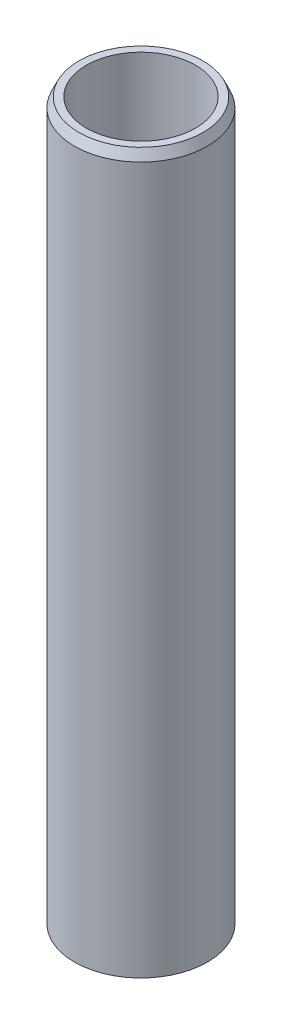
SolidWorks part; units mm, degrees
ref_plane "Front Plane" through (0, 0, 0) normal (0, 0, 1) x (1, 0, 0)
ref_plane "Top Plane" through (0, 0, 0) normal (0, 1, 0) x (1, 0, 0)
ref_plane "Right Plane" through (0, 0, 0) normal (1, 0, 0) x (0, 0, -1)
sketch "Sketch1" plane through (0, 0, 0) normal (0, 1, 0) x (1, 0, 0)
  circle A0 centre (0, 0) radius 35
  dimension "SHAFT_OD" = 70
extrude "Boss-Extrude1" add sketch "Sketch1" along normal blind 379.1822
sketch "Sketch2" plane through (0, 0, 0) normal (0, 1, 0) x (1, 0, 0)
  circle A0 centre (0, 0) radius 28.7179
  dimension "BORE_D" = 57.4358
extrude "Cut-Extrude1" cut sketch "Sketch2" along normal through all
chamfer "Chamfer1" distance 5.0816 angle 24.802 2 edges at (0, 379.1822, 35) (0, 0, 35) first distance on face at (0, 379.1822, 35) first distance on face at (0, 0, 28.7179)
